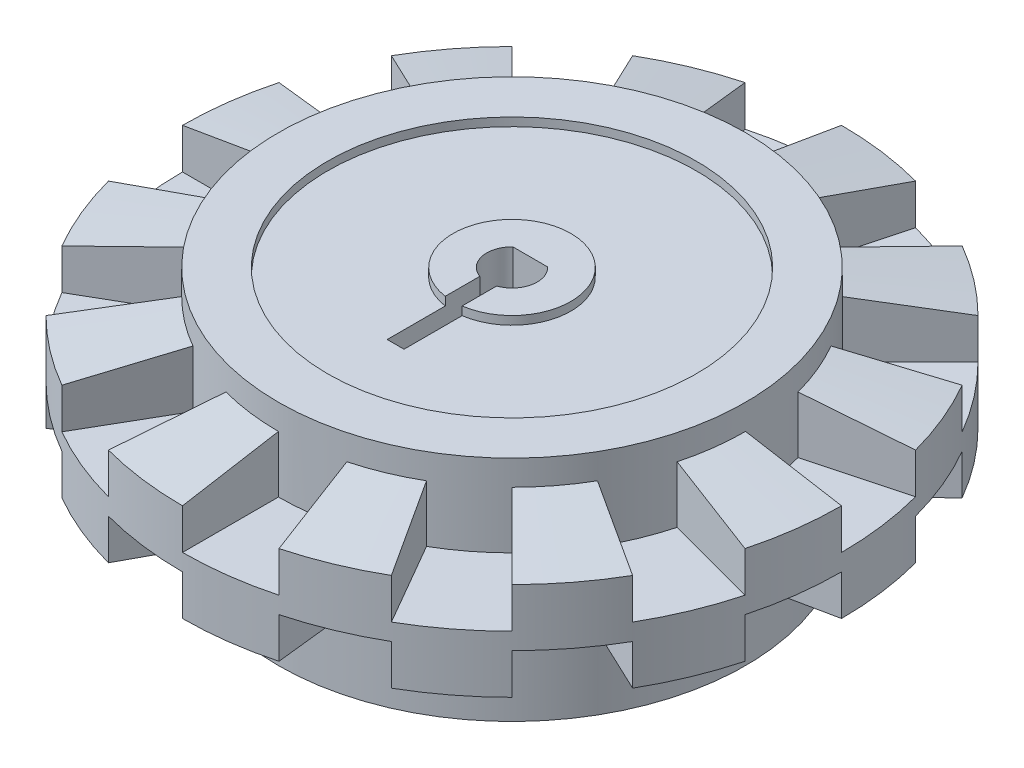
SolidWorks part; units mm, degrees
material "ABS"
ref_plane "Front Plane" through (0, 0, 0) normal (0, 0, 1) x (1, 0, 0)
ref_plane "Top Plane" through (0, 0, 0) normal (0, 1, 0) x (1, 0, 0)
ref_plane "Right Plane" through (0, 0, 0) normal (1, 0, 0) x (0, 0, -1)
ref_axis "Axis1" through (0, 6.0525, 0) along (0, -1, 0)
sketch "Sketch1" plane through (0, 0, 0) normal (1, 0, 0) x (0, 0, -1)
  line L0 (0, 13.258) -> (0, -13.742) construction
  line L14 (0, 5.375) -> (3.5, 5.375)
  line L15 (13.875, 5.375) -> (13.875, 3.875)
  line L19 (12.575, -0.2327) -> (12.575, 3.075)
  line L20 (12.575, 3.075) -> (3.5, 3.075)
  line L21 (0, 3.075) -> (0, 5.375)
  line L22 (17.5, 0) -> (0, 0) construction
  line L23 (13.875, 3.875) -> (19.575, 2.9)
  line L27 (13.875, -3.875) -> (19.575, -2.9)
  line L28 (12.575, -0.2327) -> (12.575, -8.175)
  line L29 (12.575, -8.175) -> (13.875, -8.175)
  line L30 (13.875, -8.175) -> (13.875, -3.875)
  line L31 (3.5, 5.375) -> (3.5, 4.875)
  line L32 (3.5, 4.875) -> (10.95, 4.875)
  line L33 (10.95, 4.875) -> (10.95, 5.375)
  line L34 (10.95, 5.375) -> (13.875, 5.375)
  line L35 (19.575, 2.9) -> (19.575, -2.9)
  line L36 (3.5, 3.075) -> (3.5, -0.5)
  line L37 (3.5, -0.5) -> (0, -0.5)
  line L38 (0, -0.5) -> (0, 3.075)
  dimension "D1" = 27.75
  dimension "D2" = 7
  dimension "D3" = 2.3
  dimension "D4" = 1.3
  dimension "D5" = 27
  dimension "D6" = 1.5
  dimension "D7" = 0.5
  dimension "D8" = 5.8
  dimension "D9" = 7.75
  dimension "D10" = 13.55
  dimension "D11" = 0.5
  dimension "D12" = 7
  dimension "D13" = 21.9
revolve "Revolve1" add sketch "Sketch1" angle 360 about L0
ref_plane "STOP-TOPCUT" through (0, 0.5, 0) normal (0, 1, 0) x (1, 0, 0)
sketch "Sketch4" plane through (0, 0.5, 0) normal (0, 1, 0) x (1, 0, 0)
  line L0 (0, 0) -> (0, -19.575) construction
  line L5 (0, -13.875) -> (0, -19.575)
  line L6 (3.5911, -13.4022) -> (5.0664, -18.908)
  circle A0 centre (0, 0) radius 19.575 construction
  arc A1 (5.0664, -18.908) -> (0, -19.575) centre (0, 0) cw
  arc A2 (0, -13.875) -> (3.5911, -13.4022) centre (0, 0) ccw
  circle A3 centre (0, 0) radius 13.875 construction
  dimension "D1" = 15
extrude "Cut-Topspoke" cut sketch "Sketch4" along normal blind 10
pattern_circular "Topspokes" count 12 over 360 about axis through (0, 6.0525, 0) along (0, -1, 0) of "Cut-Topspoke"
ref_plane "STOP-BOTCUT" through (0, -0.5, 0) normal (0, 1, 0) x (1, 0, 0)
sketch "Sketch5" plane through (0, -0.5, 0) normal (0, 1, 0) x (1, 0, 0)
  line L0 (0, -0.2149) -> (0, 19.575) construction
  line L1 (0, 13.875) -> (0, 19.575)
  line L2 (3.5911, 13.4022) -> (5.0664, 18.908)
  line L3 (5.0664, 18.908) -> (0, 0) construction
  arc A0 (0, 13.875) -> (3.5911, 13.4022) centre (0, 0) cw
  circle A1 centre (0, 0) radius 13.875 construction
  circle A2 centre (0, 0) radius 13.875 construction
  arc A3 (0, 19.575) -> (5.0664, 18.908) centre (0, 0) cw
  dimension "D1" = 15
extrude "Cut-Botspokes" cut sketch "Sketch5" against normal through all
pattern_circular "Botspokes" count 12 over 360 about axis through (0, 6.0525, 0) along (0, -1, 0) of "Cut-Botspokes"
sketch "Sketch6" plane through (0, 0, 0) normal (0, 1, 0) x (1, 0, 0)
  line L0 (0, 0) -> (0, -5.0623) construction
  line L1 (-1.0349, 1.0858) -> (1.0349, 1.0858)
  line L2 (-0.5, -6.9142) -> (0.5, -6.9142)
  line L3 (-0.5, -6.9142) -> (-0.5, -1.4142)
  line L5 (0.5, -6.9142) -> (0.5, -1.4142)
  line L6 (-0.5, -6.9142) -> (0.5, -1.4142) construction
  line L7 (-0.5, -1.4142) -> (0.5, -6.9142) construction
  arc A0 (-1.0349, 1.0858) -> (-0.5, -1.4142) centre (0, 0) ccw
  arc A1 (0.5, -1.4142) -> (1.0349, 1.0858) centre (0, 0) ccw
  point P3 (0, -4.1642)
  dimension "D3" = 1.5
  dimension "D1" = 5.5
  dimension "D2" = 1
  dimension "D4" = 2.5
extrude "shaft-key" cut sketch "Sketch6" along normal through all both and the other way through all
sketch "Sketch9" plane through (0, 3.075, 0) normal (0, -1, 0) x (1, 0, 0)
  line L0 (3.5, 0) -> (12.4734, 0) construction
  line L1 (3.4293, 0.7) -> (12.5555, 0.7)
  line L2 (3.4293, -0.7) -> (12.5555, -0.7)
  arc A0 (-0.5, 3.4641) -> (0.5, 3.4641) centre (0, 0) ccw construction
  arc A1 (-0.5, 3.4641) -> (0.5, 3.4641) centre (0, 0) ccw construction
  circle A2 centre (0, 0) radius 12.575 construction
  circle A3 centre (0, 0) radius 12.575 construction
  arc A4 (3.4293, 0.7) -> (3.4293, -0.7) centre (0, 0) cw
  arc A5 (12.5555, 0.7) -> (12.5555, -0.7) centre (0, 0) cw
  dimension "D1" = 1.4
extrude "Boss-Extrude1" add sketch "Sketch9" along normal offset from surface (3.175 mm away) 0.4 up to face at (0, -0.5, 0.1534)
sketch "Sketch11" plane through (0, 0, -0.7) normal (0, 0, -1) x (-1, 0, 0)
  line L1 (21.5325, 0.5) -> (-21.5325, 0.5) construction
  line L2 (-3.4293, -0.1) -> (-3.4293, 3.075) construction
  line L8 (-3.4293, 0.5) -> (-12.5555, 2.1092)
  line L12 (-12.5555, 3.075) -> (-12.5555, -0.1)
  line L13 (-12.5555, -0.1) -> (-3.4293, -0.1)
  line L14 (-3.4293, -0.1) -> (-3.4293, 3.075)
  line L15 (-3.4293, 3.075) -> (-12.5555, 3.075)
  line L16 (-12.5555, 2.1092) -> (-12.5555, -0.1)
  line L17 (-12.5555, -0.1) -> (-3.4293, -0.1)
  line L18 (-3.4293, -0.1) -> (-3.4293, 0.5)
  dimension "D1" = 0
extrude "inner-spoke" cut sketch "Sketch11" against normal up to next
pattern_circular "inner-spokes" count 6 over 360 about axis through (0, 6.0525, 0) along (0, -1, 0) of "Boss-Extrude1", "inner-spoke"
ref_plane "BearingFace" through (0, -1, 0) normal (0, -1, 0) x (-1, 0, 0)
